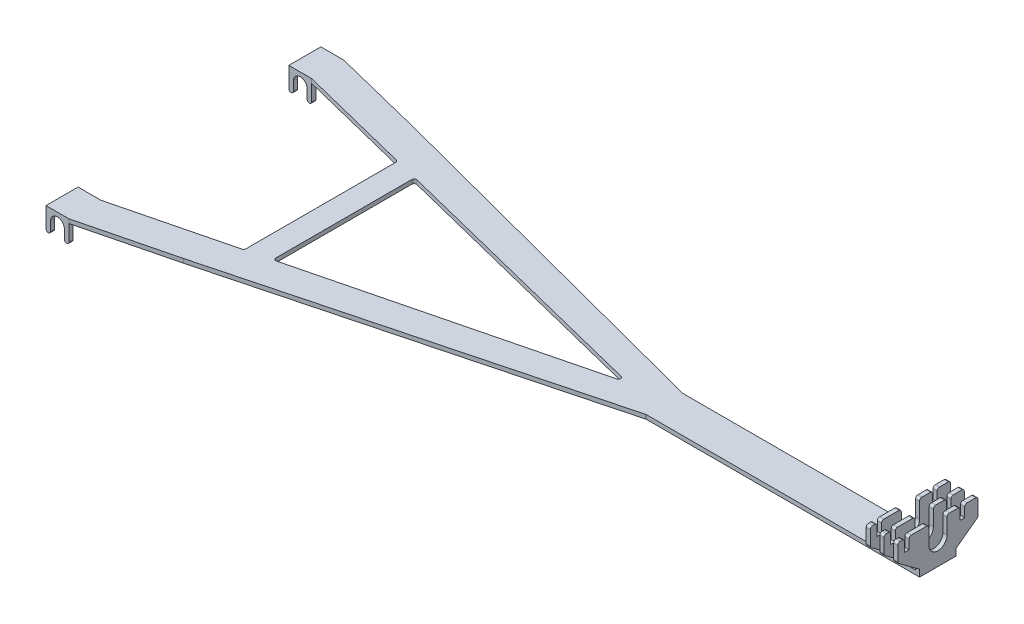
SolidWorks part; units mm, degrees
ref_plane "Front Plane" through (0, 0, 0) normal (0, 0, 1) x (1, 0, 0)
ref_plane "Top Plane" through (0, 0, 0) normal (0, 1, 0) x (1, 0, 0)
ref_plane "Right Plane" through (0, 0, 0) normal (1, 0, 0) x (0, 0, -1)
sketch "Sketch1" plane through (0, 0, 0) normal (0, 1, 0) x (1, 0, 0)
  line L0 (-450, 300) -> (-400, 300)
  line L1 (-400, 300) -> (-200, 250)
  line L2 (-200, 250) -> (200, 250) construction
  line L3 (200, 250) -> (600, 40) construction
  line L4 (600, 40) -> (1200, 40)
  line L5 (-450, -300) -> (-400, -300)
  line L6 (-400, -300) -> (-200, -250)
  line L7 (-200, -250) -> (200, -250) construction
  line L8 (200, -250) -> (600, -40) construction
  line L9 (600, -40) -> (1200, -40)
  line L10 (600, 40) -> (600, -40) construction
  line L11 (200, -250) -> (200, 250) construction
  line L12 (-200, 250) -> (-200, -250) construction
  line L13 (-400, -300) -> (-400, 300) construction
  line L14 (0, 0) -> (200, 0) construction
  line L15 (0, 250) -> (0, 0) construction
  line L16 (1200, 40) -> (1200, -40)
  line L17 (-450, 300) -> (-450, -300)
  line L18 (600, 0) -> (200, 0) construction
  line L19 (-450, 0) -> (-400, 0) construction
  line L20 (-400, 0) -> (-200, 0) construction
  line L21 (-200, 0) -> (0, 0) construction
  line L22 (-200, 250) -> (600, 40)
  line L23 (600, -40) -> (-200, -250)
  dimension "D1" = 600
  dimension "D2" = 200
  dimension "D3" = 50
  dimension "D4" = 400
  dimension "D5" = 500
  dimension "D6" = 80
  dimension "D7" = 600
  dimension "D8" = 400
extrude "Boss-Extrude1" add sketch "Sketch1" along normal blind 15
sketch "Sketch2" plane through (0, 0, 0) normal (0, 0, 1) x (1, 0, 0)
  line L0 (-450, 0) -> (-450, -40)
  line L1 (-450, -40) -> (-400, -40)
  line L2 (-400, -40) -> (-400, 0)
  line L3 (-400, 0) -> (-200, 0) construction
  line L4 (-400, 0) -> (-450, 0)
  line L5 (-440, -15) -> (-440, -40)
  line L6 (-410, -15) -> (-410, -40)
  line L7 (-425, 0) -> (-425, -15) construction
  circle A0 centre (-425, -15) radius 15
  dimension "D1" = 30
  dimension "D2" = 40
extrude "Boss-Extrude2" add sketch "Sketch2" along normal up to surface and the other way up to surface contours L4 L7 A0 L6 L1 L2 | L7 L4 L0 L1 L5 A0 region at (-444.1006, -18.2067, 0) region at (-405.8994, -18.2067, 0) up to face at (-425, 7.5, 300) other way up to face at (-425, 7.5, -300)
sketch "Sketch4" plane through (0, 0, 0) normal (0, 1, 0) x (1, 0, 0)
  line L0 (-450, 230) -> (-400, 230)
  line L1 (-450, 300) -> (-450, -300) construction
  line L2 (-400, 230) -> (-150, 167.5)
  line L3 (-150, 167.5) -> (-150, -167.5)
  line L4 (-150, -167.5) -> (-400, -230)
  line L5 (-400, -230) -> (-450, -230)
  line L6 (-400, 230) -> (-400, -230) construction
  line L7 (-200, 250) -> (-200, -250) construction
  line L9 (-200, 0) -> (-150, 0) construction
  line L10 (-400, -230) -> (-400, -300) construction
  line L11 (-400, -300) -> (-200, -250) construction
  line L12 (-450, 230) -> (-450, -230)
  line L14 (-200, 250) -> (-400, 300) construction
  line L15 (-100, 155) -> (-100, -155)
  line L16 (-100, -155) -> (520, 0)
  line L17 (520, 0) -> (-100, 155)
  line L18 (520, 0) -> (-100, 0) construction
  dimension "D1" = 460
  dimension "D2" = 300
  dimension "D3" = 50
extrude "Cut-Extrude2" cut sketch "Sketch4" against normal through all both and the other way through all
sketch "Sketch5" plane through (0, 0, 0) normal (1, 0, 0) x (0, 0, -1)
  line L0 (-300, 0) -> (-230, 0) construction
  line L1 (-285, 0) -> (-245, 0)
  line L2 (-285, 0) -> (-285, -40)
  line L3 (-285, -40) -> (-245, -40)
  line L4 (-245, 0) -> (-245, -40)
  line L5 (-300, -40) -> (-230, -40) construction
  line L6 (230, 0) -> (300, 0) construction
  line L7 (245, 0) -> (285, 0)
  line L8 (245, 0) -> (245, -40)
  line L9 (245, -40) -> (285, -40)
  line L10 (285, 0) -> (285, -40)
  line L11 (230, -40) -> (300, -40) construction
  line L12 (-300, 0) -> (-300, -40) construction
  line L13 (230, -40) -> (230, 0) construction
  line L14 (300, 0) -> (300, -40) construction
  dimension "D1" = 15
  dimension "D2" = 15
  dimension "D3" = 15
  dimension "D4" = 15
extrude "Cut-Extrude3" cut sketch "Sketch5" against normal through all
sketch "Sketch7" plane through (1200, 0, 0) normal (1, 0, 0) x (0, 0, -1)
  line L1 (-40, 15) -> (-87.5, 50)
  line L2 (-87.5, 50) -> (-87.5, 88.7)
  line L3 (-87.5, 88.7) -> (87.5, 88.7)
  line L4 (87.5, 88.7) -> (87.5, 50)
  line L5 (87.5, 50) -> (40, 15)
  line L7 (-40, 15) -> (40, 15)
  line L8 (-20, 50) -> (-20, 88.7)
  line L9 (87.5, 50) -> (-87.5, 50) construction
  line L10 (0, 88.7) -> (0, 50) construction
  line L11 (-20, 88.7) -> (20, 88.7)
  line L12 (0, 50) -> (0, 0) construction
  line L13 (20, 88.7) -> (20, 50)
  line L14 (-73, 88.7) -> (-63, 88.7)
  line L15 (-73, 88.7) -> (-73, 63.2)
  line L16 (-73, 63.2) -> (-63, 63.2)
  line L17 (-63, 88.7) -> (-63, 63.2)
  line L18 (48.5, 88.7) -> (58.5, 88.7)
  line L19 (48.5, 88.7) -> (48.5, 63.2)
  line L20 (48.5, 63.2) -> (58.5, 63.2)
  line L21 (58.5, 88.7) -> (58.5, 63.2)
  circle A0 centre (0, 50) radius 20
  line M14 (40, 15) -> (-40, 15)
  dimension "D3" = 40
  dimension "D1" = 175
  dimension "D2" = 50
  dimension "D4" = 25.5
  dimension "D5" = 10
  dimension "D6" = 63
  dimension "D7" = 48.5
  dimension "D8" = 38.7
extrude "Boss-Extrude4" add sketch "Sketch7" against normal blind 75 contours L3 L21 L20 L19 L17 L16 L15 L2 L1 L5 L4 M14 region at (1200, 34.0287, 62.6236)
sketch "Sketch8" plane through (0, 0, 0) normal (0, 0, 1) x (1, 0, 0)
  line L0 (1125, 88.7) -> (1200, 88.7) construction
  line L1 (1140, 88.7) -> (1185, 88.7)
  line L2 (1140, 88.7) -> (1140, 15)
  line L3 (1140, 15) -> (1185, 15)
  line L4 (1185, 88.7) -> (1185, 15)
  line L5 (1125, 15) -> (1200, 15) construction
  line L6 (1125, 50) -> (1125, 88.7) construction
  line L7 (1200, 50) -> (1200, 88.7) construction
  line L8 (1155, 88.7) -> (1170, 88.7) construction
  line L9 (1155, 88.7) -> (1170, 88.7)
  line L10 (1155, 88.7) -> (1155, 15)
  line L11 (1155, 15) -> (1170, 15)
  line L12 (1170, 88.7) -> (1170, 15)
  line L15 (1162.5, 50) -> (1162.5, 88.7) construction
  line L16 (1125, 50) -> (1200, 50) construction
  line L17 (1155, 88.7) -> (1170, 88.7) construction
  dimension "D1" = 15
  dimension "D2" = 15
  dimension "D3" = 15
extrude "Cut-Extrude4" cut sketch "Sketch8" against normal through all both and the other way through all contours L10 L1 L2 L3 | L1 L12 L3 L4 region at (1147.5, 51.85, 0) region at (1177.5, 51.85, 0)
fillet "Fillet1" radius 5 53 edges at (1192.5, 50, 87.5) (1162.5, 50, 87.5) (1132.5, 50, 87.5) (1192.5, 50, -87.5) (1162.5, 50, -87.5) (1132.5, 50, -87.5) (1192.5, 88.7, -87.5) (1162.5, 88.7, -87.5) (1132.5, 88.7, -87.5) (1132.5, 88.7, -58.5) (1162.5, 88.7, -58.5) (1192.5, 88.7, -58.5) (1192.5, 88.7, -48.5) (1162.5, 88.7, -48.5) (1132.5, 88.7, -48.5) (1192.5, 88.7, -20) (1162.5, 88.7, -20) (1132.5, 88.7, -20) (1192.5, 88.7, 63) (1162.5, 88.7, 63) (1132.5, 88.7, 63) (1132.5, 88.7, 87.5) (1162.5, 88.7, 87.5) (1192.5, 88.7, 87.5) (1192.5, 88.7, 73) (1162.5, 88.7, 73) (1132.5, 88.7, 73) (1192.5, 88.7, 20) (1162.5, 88.7, 20) (1132.5, 88.7, 20) (600, 7.5, 40) (600, 7.5, -40) (520, 7.5, 0) (-440, -40, -292.5) (-440, -40, -237.5) (-400, -40, -292.5) (-400, -40, -237.5) (-450, -40, -237.5) (-410, -40, -237.5) (-450, -40, -292.5) (-410, -40, -292.5) (-150, 7.5, 167.5) (-100, 7.5, 155) (-150, 7.5, -167.5) (-100, 7.5, -155) (-450, -40, 237.5) (-410, -40, 237.5) (-440, -40, 237.5) (-400, -40, 237.5) (-450, -40, 292.5) (-440, -40, 292.5) (-400, -40, 292.5) (-410, -40, 292.5)
sketch "Sketch9" plane through (0, 0, 0) normal (0, 0, 1) x (1, 0, 0)
  line L0 (-400, 0) -> (-200, 0) construction
  line L1 (-450, 15) -> (1125, 15)
  line L2 (-450, 15) -> (-450, 9)
  line L3 (-450, 9) -> (1125, 9)
  line L4 (1125, 15) -> (1125, 9)
  line L5 (1140, 15) -> (1155, 15)
  line L6 (1140, 15) -> (1140, 9)
  line L7 (1140, 9) -> (1155, 9)
  line L8 (1155, 15) -> (1155, 9)
  line L9 (1170, 15) -> (1185, 15)
  line L10 (1170, 15) -> (1170, 9)
  line L11 (1170, 9) -> (1185, 9)
  line L12 (1185, 15) -> (1185, 9)
  line L13 (1125, 88.7) -> (1140, 88.7) construction
  line L14 (1125, 88.7) -> (1128, 88.7)
  line L15 (1125, 88.7) -> (1125, 9)
  line L16 (1125, 9) -> (1128, 9)
  line L17 (1128, 88.7) -> (1128, 9)
  line L18 (1137, 88.7) -> (1158, 88.7)
  line L19 (1137, 88.7) -> (1137, 9)
  line L20 (1137, 9) -> (1158, 9)
  line L21 (1158, 88.7) -> (1158, 9)
  line L22 (1155, 88.7) -> (1170, 88.7) construction
  line L23 (1167, 88.7) -> (1188, 88.7)
  line L24 (1167, 88.7) -> (1167, 9)
  line L25 (1167, 9) -> (1188, 9)
  line L26 (1188, 88.7) -> (1188, 9)
  line L27 (1185, 88.7) -> (1200, 88.7) construction
  line L28 (1197, 88.7) -> (1200, 88.7)
  line L29 (1197, 88.7) -> (1197, 9)
  line L30 (1197, 9) -> (1200, 9)
  line L31 (1200, 88.7) -> (1200, 9)
  line L32 (1200, 15) -> (1200, 0) construction
  line L33 (1125, 12) -> (1128, 12) construction
  line L34 (1140, 12) -> (1137, 12) construction
  line L35 (600.6453, 0) -> (1200, 0) construction
  line L36 (1197, 9) -> (1200, 9)
  line L37 (1197, 9) -> (1197, 0)
  line L38 (1197, 0) -> (1200, 0)
  line L39 (1200, 9) -> (1200, 0)
  point P50 (1200, -0.034)
  point P51 (1200, 0)
  point P52 (1197, 0)
  dimension "D1" = 9
  dimension "D2" = 9
  dimension "D3" = 9
  dimension "D4" = 9
extrude "Cut-Extrude5" cut sketch "Sketch9" against normal through all both and the other way through all contours L26 L23 L24 L25 L10 L9 L12 | L21 L18 L19 L20 L6 L5 L8 | L8 L5 L6 L7 | L12 L9 L10 L11 | L31 L28 L29 L30 | L17 L14 L15 L4 L16 | L4 L1 L2 L3 | L39 L30 L37 L38 region at (337.5, 12, 0) region at (1126.5, 48.85, 0) region at (1147.5, 50.9441, 0) region at (1147.5, 12, 0) region at (1177.5, 50.9441, 0) region at (1177.5, 12, 0) region at (1198.5, 48.85, 0) region at (1198.5, 4.5, 0)
sketch "Sketch10" plane through (-450, 0, 0) normal (-1, 0, 0) x (0, 0, 1)
  line L0 (285, -40) -> (300, -40) construction
  line L1 (239, 0) -> (291, 0)
  line L2 (239, 0) -> (239, -40)
  line L3 (239, -40) -> (291, -40)
  line L4 (291, 0) -> (291, -40)
  line L5 (245, 0) -> (285, 0) construction
  line L8 (230, -35) -> (230, 9) construction
  line L9 (300, 9) -> (300, -35) construction
  line L10 (0, 170.2561) -> (0, -166.8858) construction
  line L11 (-291, 0) -> (-291, -40)
  line L12 (-239, -40) -> (-291, -40)
  line L13 (-239, 0) -> (-239, -40)
  line L14 (-239, 0) -> (-291, 0)
  dimension "D1" = 9
  dimension "D2" = 9
extrude "Cut-Extrude6" cut sketch "Sketch10" against normal up to surface (50 mm away) up to face at (-400, -17.5, 237.5)
